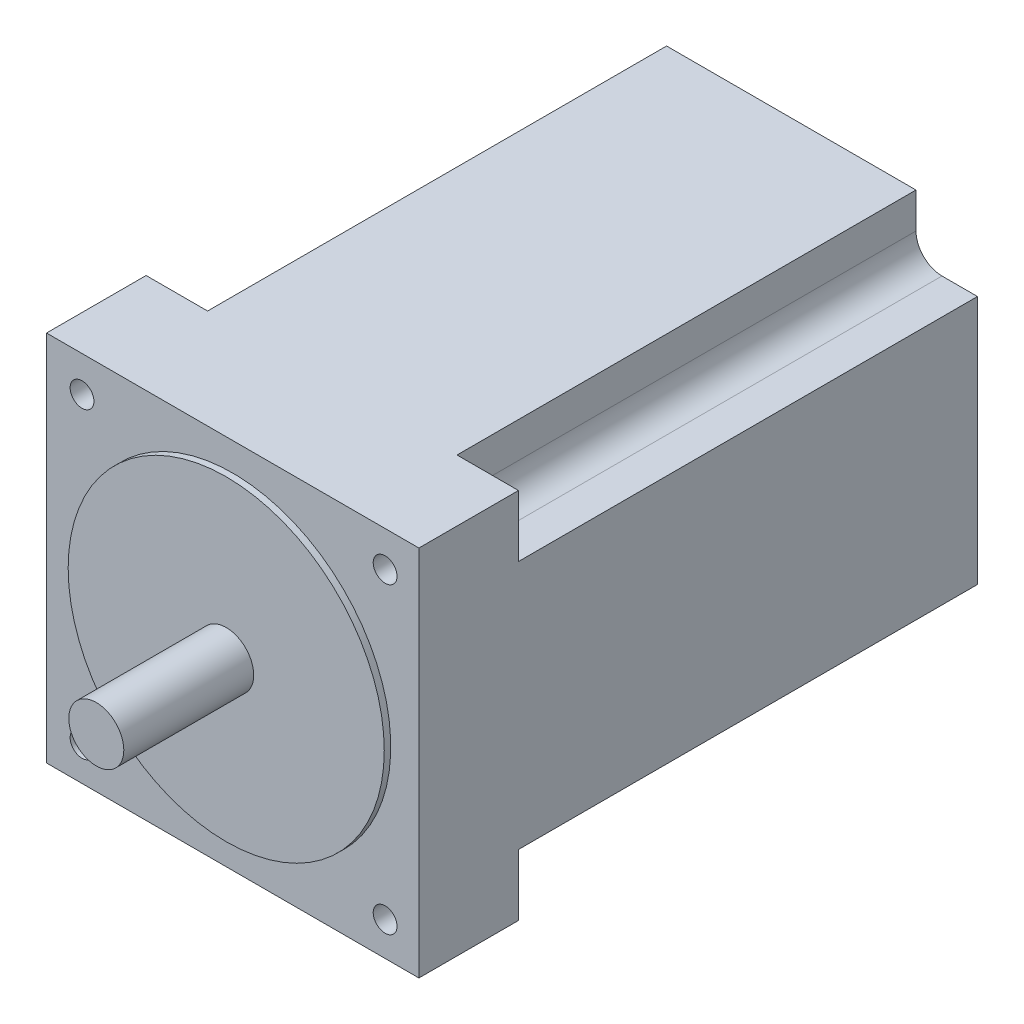
SolidWorks part; units mm, degrees
ref_plane "前视基准面" through (0, 0, 0) normal (0, 0, 1) x (1, 0, 0)
ref_plane "上视基准面" through (0, 0, 0) normal (0, 1, 0) x (1, 0, 0)
ref_plane "右视基准面" through (0, 0, 0) normal (1, 0, 0) x (0, 0, -1)
sketch "草图3" plane through (0, 0, 0) normal (0, 0, 1) x (1, 0, 0)
  line L1 (-43, -43) -> (43, -43)
  line L2 (-43, -43) -> (-43, 43)
  line L3 (-43, 43) -> (43, 43)
  line L4 (43, -43) -> (43, 43)
  line L5 (-43, -43) -> (43, 43) construction
  line L6 (-43, 43) -> (43, -43) construction
  point P0 (0, 0)
  dimension "D1" = 86
extrude "凸台-拉伸2" add sketch "草图3" along normal mid plane 129
sketch "草图4" plane through (0, 0, -64.5) normal (0, 0, -1) x (-1, 0, 0)
  line L0 (0, 0) -> (0, 51.8163) construction
  line L1 (0, 0) -> (-61.1756, 0) construction
  line L2 (-28.8, 34.8) -> (-28.8, 43)
  line L3 (-34.8, 28.8) -> (-43, 28.8)
  line L4 (-28.8, 28.8) -> (-28.8, 51.8163) construction
  line L5 (-28.8, 28.8) -> (-61.1756, 28.8) construction
  line L6 (-43, 43) -> (-28.8, 43)
  line L8 (-43, 43) -> (-43, 28.8)
  arc A0 (-28.8, 34.8) -> (-34.8, 28.8) centre (-34.8, 34.8) cw
  dimension "D2" = 6
  dimension "D1" = 28.8
extrude "切除-拉伸2" cut sketch "草图4" against normal blind 106
ref_axis "基准轴2" through (0, 0, -44) along (0, 0, 1)
pattern_circular "阵列(圆周)1" count 4 over 360 about axis through (0, 0, -44) along (0, 0, 1) of "切除-拉伸2"
sketch "草图5" plane through (0, 0, 64.5) normal (0, 0, 1) x (1, 0, 0)
  line L3 (-34.8, -35.2) -> (35.2, -35.2) construction
  line L4 (-34.8, -35.2) -> (-34.8, 34.8) construction
  line L5 (-34.8, 34.8) -> (35.2, 34.8) construction
  line L6 (35.2, -35.2) -> (35.2, 34.8) construction
  line L7 (-34.8, -35.2) -> (35.2, 34.8) construction
  line L8 (-34.8, 34.8) -> (35.2, -35.2) construction
  circle A0 centre (-34.8, 34.8) radius 2.75
  circle A1 centre (35.2, 34.8) radius 2.75
  circle A2 centre (35.2, -35.2) radius 2.75
  circle A3 centre (-34.8, -35.2) radius 2.75
  dimension "D2" = 5.5
  dimension "D1" = 70
  dimension "D3" = 70
extrude "切除-拉伸3" cut sketch "草图5" against normal blind 10
sketch "草图6" plane through (0, 0, 64.5) normal (0, 0, 1) x (1, 0, 0)
  circle A0 centre (0, 0) radius 36.5
  dimension "D1" = 73
extrude "凸台-拉伸3" add sketch "草图6" along normal blind 1.5
sketch "草图7" plane through (0, 0, 66) normal (0, 0, 1) x (1, 0, 0)
  circle A0 centre (0, 0) radius 6.35
  dimension "D1" = 12.7
extrude "凸台-拉伸4" add sketch "草图7" along normal blind 30
